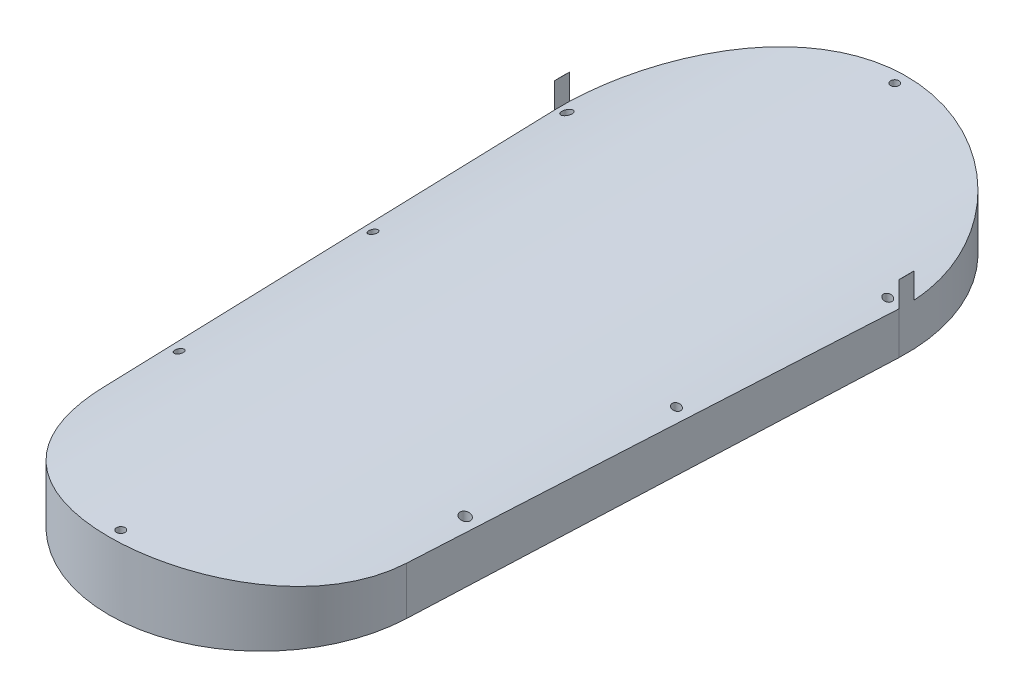
SolidWorks part; units mm, degrees
ref_plane "Front Plane" through (0, 0, 0) normal (0, 0, 1) x (1, 0, 0)
ref_plane "Top Plane" through (0, 0, 0) normal (0, 1, 0) x (1, 0, 0)
ref_plane "Right Plane" through (0, 0, 0) normal (1, 0, 0) x (0, 0, -1)
sketch "Sketch1" plane through (0, 0, 0) normal (0, 1, 0) x (1, 0, 0)
  line L0 (90.177, -149.3379) -> (102.1659, 130.1479)
  line L1 (-101.6466, 130.1479) -> (-89.6577, -149.3379)
  line L2 (-93.1597, 118.9687) -> (-89.0054, 22.1229)
  line L3 (-87.1819, -20.3849) -> (-88.0169, -0.921)
  line L4 (-86.676, -32.1794) -> (-87.1819, -20.3849)
  line L5 (-83.8625, -97.7668) -> (-86.676, -32.1794)
  line L6 (-81.665, -148.995) -> (-82.874, -120.8107)
  line L7 (83.3933, -120.8107) -> (82.1843, -148.995)
  line L8 (84.3818, -97.7668) -> (88.5362, -0.921)
  line L9 (89.5247, 22.1229) -> (93.679, 118.9687)
  line L10 (93.679, 118.9687) -> (91.6277, 71.1483)
  arc A0 (-89.6577, -149.3379) -> (90.177, -149.3379) centre (0.2596, -145.4807) ccw
  arc A1 (102.1659, 130.1479) -> (-101.6466, 130.1479) centre (0.2596, 134.5193) ccw
  arc A2 (-11.5067, 227.78) -> (-93.4196, 142.2779) centre (0.2596, 134.5193) ccw
  arc A3 (93.9389, 142.2779) -> (12.026, 227.78) centre (0.2596, 134.5193) ccw
  arc A4 (-6.596, 225.3962) -> (7.1153, 225.3962) centre (0.2596, 229.5193) ccw
  circle A5 centre (95.1724, 130.4479) radius 2.5
  circle A6 centre (90.0295, 10.5581) radius 2.5
  arc A7 (-93.4196, 142.2779) -> (-90.8276, 137.4739) centre (-88.4367, 141.8652) ccw
  circle A8 centre (-94.6531, 130.4479) radius 3.025
  arc A9 (-90.66, 123.5157) -> (-90.8276, 137.4739) centre (-94.6531, 130.4479) ccw
  arc A10 (-90.66, 123.5157) -> (-93.1597, 118.9687) centre (-88.1643, 119.183) ccw
  circle A11 centre (-89.5102, 10.5581) radius 2.5
  arc A12 (-85.5171, 3.6259) -> (-86.1255, 17.8068) centre (-89.5102, 10.5581) ccw
  arc A13 (-85.5171, 3.6259) -> (-88.0169, -0.921) centre (-83.0215, -0.7067) ccw
  circle A14 centre (84.8866, -109.3316) radius 3.025
  circle A15 centre (0.2596, -228.4807) radius 2.5
  circle A16 centre (-84.3674, -109.3316) radius 2.5
  arc A17 (-83.8625, -97.7668) -> (-80.9826, -102.0829) centre (-78.8671, -97.5525) ccw
  arc A18 (-80.3743, -116.2638) -> (-80.9826, -102.0829) centre (-84.3674, -109.3316) ccw
  arc A19 (-80.3743, -116.2638) -> (-82.874, -120.8107) centre (-77.8786, -120.5965) ccw
  arc A20 (-81.665, -148.995) -> (-11.5387, -226.6275) centre (0.2596, -145.4807) ccw
  arc A21 (-11.5387, -226.6275) -> (-6.5582, -224.2954) centre (-10.8193, -221.6795) ccw
  arc A22 (7.0775, -224.2954) -> (-6.5582, -224.2954) centre (0.2596, -228.4807) ccw
  arc A23 (7.0775, -224.2954) -> (12.058, -226.6275) centre (11.3386, -221.6795) ccw
  arc A24 (12.058, -226.6275) -> (82.1843, -148.995) centre (0.2596, -145.4807) ccw
  arc A25 (83.3933, -120.8107) -> (80.8936, -116.2638) centre (78.3979, -120.5965) ccw
  arc A26 (81.5019, -102.0829) -> (80.8936, -116.2638) centre (84.8866, -109.3316) ccw
  arc A27 (81.5019, -102.0829) -> (84.3818, -97.7668) centre (79.3864, -97.5525) ccw
  arc A28 (88.5362, -0.921) -> (86.0364, 3.6259) centre (83.5408, -0.7067) ccw
  arc A29 (86.6447, 17.8068) -> (86.0364, 3.6259) centre (90.0295, 10.5581) ccw
  arc A30 (86.6447, 17.8068) -> (89.5247, 22.1229) centre (84.5293, 22.3372) ccw
  arc A31 (93.679, 118.9687) -> (91.1793, 123.5157) centre (88.6836, 119.183) ccw
  arc A32 (91.3469, 137.4739) -> (91.1793, 123.5157) centre (95.1724, 130.4479) ccw
  arc A33 (91.3469, 137.4739) -> (93.9389, 142.2779) centre (88.956, 141.8652) ccw
  circle A34 centre (0.2596, 229.5193) radius 2.5
  arc A35 (-6.596, 225.3962) -> (-11.5067, 227.78) centre (-10.8808, 222.8193) ccw
  arc A36 (12.026, 227.78) -> (7.1153, 225.3962) centre (11.4001, 222.8193) ccw
  arc A37 (-89.0054, 22.1229) -> (-86.1255, 17.8068) centre (-84.01, 22.3372) ccw
extrude "Boss-Extrude1" add sketch "Sketch1" along normal blind 10 contours L0 A1 L1 A0 A37 L2 A10 A9 A7 A2 A35 A4 A36 A3 A33 A32 A31 L9 A30 A29 A28 L8 A27 A26 A25 L7 A24 A23 A22 A21 A20 L6 A19 A18 A17 L5 L4 L3 A13 A12 A34 A16 A15 A14 region at (0.2596, 0, 234.9665)
extrude "Boss-Extrude2" add sketch "Sketch1<3>" along normal blind 30 from offset 10 contours L2 A37 A12 A13 L3 L4 L5 A17 A18 A19 L6 A20 A21 A22 A23 A24 L7 A25 A26 A27 L8 A28 A29 A30 L9 A31 A32 A33 A3 A36 A4 A35 A2 A7 A9 A10 | L0 A1 L1 A0 A37 L2 A10 A9 A7 A2 A35 A4 A36 A3 A33 A32 A31 L9 A30 A29 A28 L8 A27 A26 A25 L7 A24 A23 A22 A21 A20 L6 A19 A18 A17 L5 L4 L3 A13 A12 A34 A16 A15 A14 region at (0.2596, 0, 234.9665) region at (0.2596, 0, -5.4407)
sketch "Sketch1<3>" plane through (0, 0, 0) normal (0, 1, 0) x (1, 0, 0) same geometry as "Sketch1"
sketch "Sketch2" plane through (0, 0, 0) normal (0, 0, 1) x (1, 0, 0)
  line L0 (-101.6466, 40) -> (-101.6466, 0) construction
  line L1 (102.1659, 40) -> (102.1659, 0) construction
  line L2 (-101.6466, 25) -> (102.1659, 25) construction
  line L3 (90.177, 40) -> (-89.6577, 40) construction
  line L4 (-101.6466, 25) -> (-101.6466, 40)
  line L5 (-101.6466, 40) -> (102.1659, 40)
  line L6 (102.1659, 40) -> (102.1659, 25)
  arc A0 (-101.6466, 25) -> (102.1659, 25) centre (0.2596, -313.663) cw
  dimension "D1" = 15
extrude "Cut-Extrude1" cut sketch "Sketch2" against normal through all both and the other way through all contours L4 A0 L5 | L5 A0 L6 region at (76.7987, 35.5168, 0) region at (-76.2794, 35.5168, 0)
sketch "Sketch4" plane through (0, 0, 0) normal (1, 0, 0) x (0, 0, -1)
  line L0 (-235.4807, 40) -> (-235.4807, 0) construction
  line L1 (-235.4807, 25) -> (-235.4807, 40)
  line L2 (-235.4807, 40) -> (236.5193, 40)
  line L3 (236.5193, 40) -> (236.5193, 25)
  line L4 (-235.4807, 25) -> (236.5193, 25) construction
  arc A0 (-235.4807, 25) -> (236.5193, 25) centre (0.5193, -1824.0333) cw
  dimension "D1" = 15
extrude "Cut-Extrude2" [suppressed] cut sketch "Sketch4" against normal through all both and the other way through all contours L2 A0 L3 | L1 A0 L2
